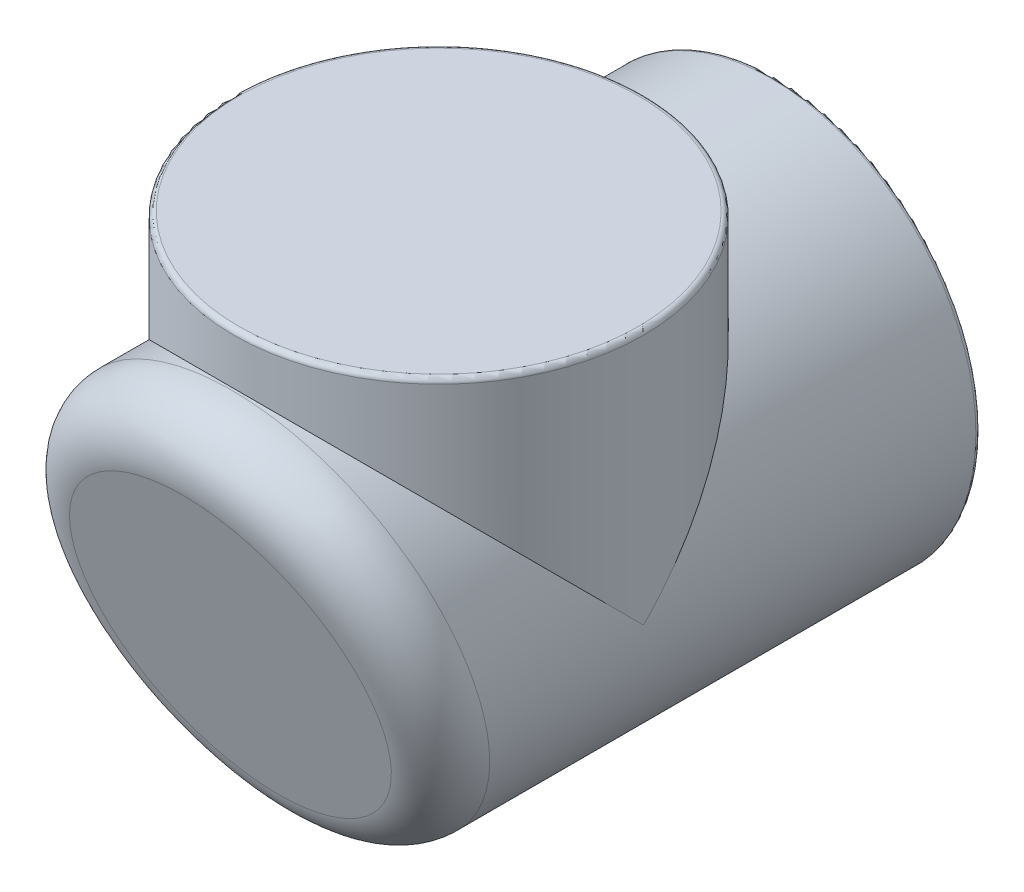
SolidWorks part; units mm, degrees
ref_plane "Front Plane" through (0, 0, 0) normal (0, 0, 1) x (1, 0, 0)
ref_plane "Top Plane" through (0, 0, 0) normal (0, 1, 0) x (1, 0, 0)
ref_plane "Right Plane" through (0, 0, 0) normal (1, 0, 0) x (0, 0, -1)
sketch "Sketch2" plane through (0, 0, 0) normal (0, 0, 1) x (1, 0, 0)
  circle A0 centre (0, 0) radius 40
  dimension "D1" = 80
extrude "Boss-Extrude1" add sketch "Sketch2" along normal mid plane 120
sketch "Sketch3" plane through (0, 0, 0) normal (1, 0, 0) x (0, 0, -1)
  line L0 (-60, 40) -> (-35, -40)
  line L1 (-60, -40) -> (60, -40) construction
  line L2 (-35, -40) -> (-60, -40)
  line L3 (-60, -40) -> (-60, 40)
  dimension "D1" = 25
extrude "Cut-Extrude1" cut sketch "Sketch3" against normal through all both and the other way through all
fillet "Fillet1" radius 10 1 edges at (0, -40, 35)
sketch "Sketch4" plane through (0, 0, 0) normal (0, 1, 0) x (1, 0, 0)
  line L0 (40, 60) -> (-40, 60) construction
  circle A0 centre (0, -5.9) radius 40
  dimension "D2" = 80
  dimension "D1" = 65.9
extrude "Boss-Extrude2" add sketch "Sketch4" along normal blind 50
fillet "Fillet2" radius 1 2 edges at (0, 50, 45.9) (40, 0, -60)
sketch "Sketch5" plane through (0, 0, 0) normal (0, 1, 0) x (1, 0, 0)
  line L0 (0, 59) -> (0, -44.9) construction
  line L1 (40, 59) -> (-40, 59) construction
  circle A0 centre (0, -5.9) radius 39 construction
  point P7 (0, -5.9)
